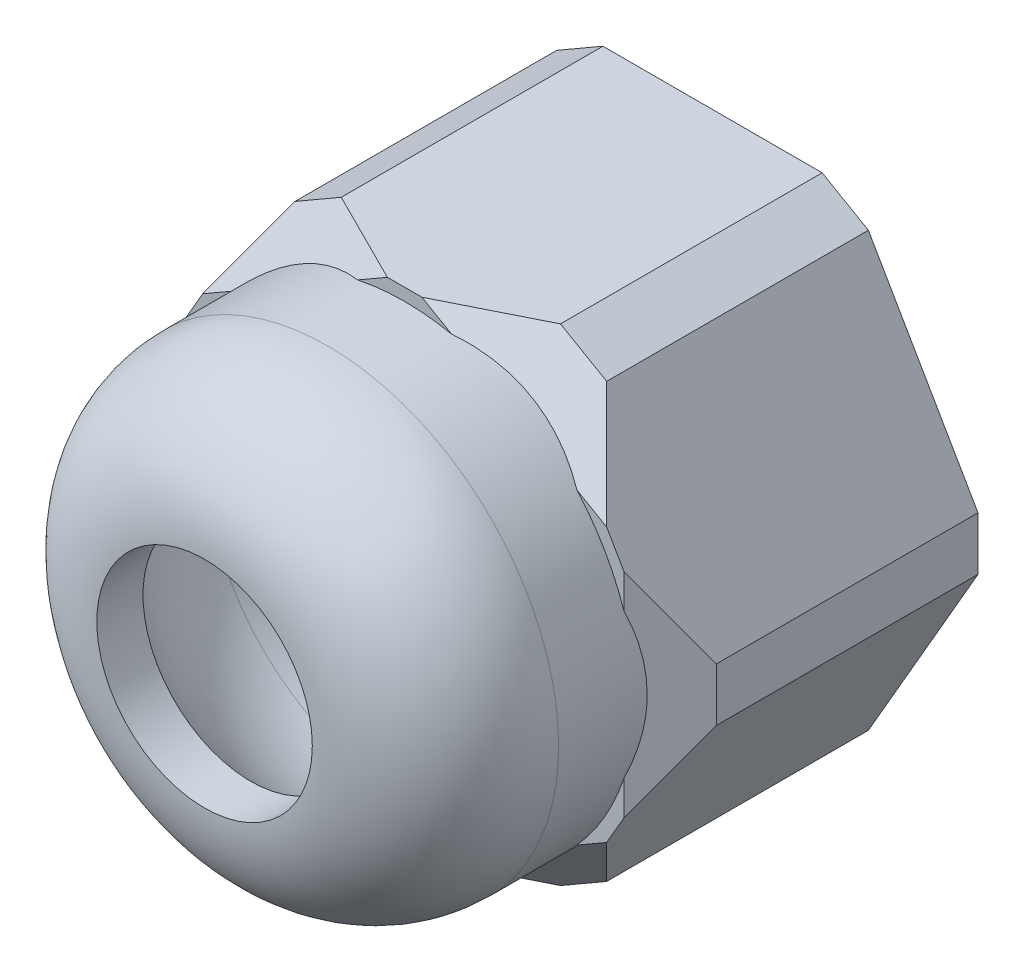
SolidWorks part; units mm, degrees
ref_plane "Front Plane" through (0, 0, 0) normal (0, 0, 1) x (1, 0, 0)
ref_plane "Top Plane" through (0, 0, 0) normal (0, 1, 0) x (1, 0, 0)
ref_plane "Right Plane" through (0, 0, 0) normal (1, 0, 0) x (0, 0, -1)
sketch "Sketch1" plane through (0, 0, 0) normal (0, 0, 1) x (1, 0, 0)
  line L1 (-9.1221, 0) -> (-4.5611, -7.9)
  line L2 (-4.5611, -7.9) -> (4.5611, -7.9)
  line L3 (4.5611, -7.9) -> (9.1221, 0)
  line L4 (9.1221, 0) -> (4.5611, 7.9)
  line L5 (4.5611, 7.9) -> (-4.5611, 7.9)
  line L6 (-4.5611, 7.9) -> (-9.1221, 0)
  circle A0 centre (0, 0) radius 7.9 construction
  dimension "D1" = 15.8
extrude "Boss-Extrude1" add sketch "Sketch1" along normal blind 10
sketch "Sketch3" plane through (0, 0, 0) normal (1, 0, 0) x (0, 0, -1)
  line L0 (-10, 7.5) -> (-12.5, 7.5)
  line L1 (-10, 0) -> (-10, 7.9) construction
  line L2 (-16.5, 3.5) -> (-15, 3.5)
  line L4 (-10, 6.5) -> (-10, 7.5)
  line L5 (-20.3861, 0) -> (4.9973, 0) construction
  arc A0 (-12.5, 7.5) -> (-16.5, 3.5) centre (-12.5, 3.5) ccw
  arc A1 (-15, 3.5) -> (-10, 6.5) centre (-10, 0.8333) cw
  dimension "D1" = 7.5
  dimension "D2" = 2.5
  dimension "D3" = 3.5
  dimension "D4" = 6.5
  dimension "D5" = 1.5
revolve "Revolve1" add sketch "Sketch3" angle 360 about L5
sketch "Sketch4" plane through (0, 0, 10) normal (0, 0, 1) x (1, 0, 0)
  circle A0 centre (0, 0) radius 6.5
  circle A1 centre (0, 0) radius 6.5 construction
extrude "Cut-Extrude1" cut sketch "Sketch4" against normal up to next
chamfer "Chamfer1" distance 1 6 edges at (-4.5611, 7.9, 5) (-9.1221, 0, 5) (-4.5611, -7.9, 5) (4.5611, -7.9, 5) (9.1221, 0, 5) (4.5611, 7.9, 5)
chamfer "Chamfer2" distance 1.5 6 edges at (-4.3111, 7.467, 10) (-8.6221, 0, 10) (-4.3111, -7.467, 10) (4.3111, -7.467, 10) (8.6221, 0, 10) (4.3111, 7.467, 10)
